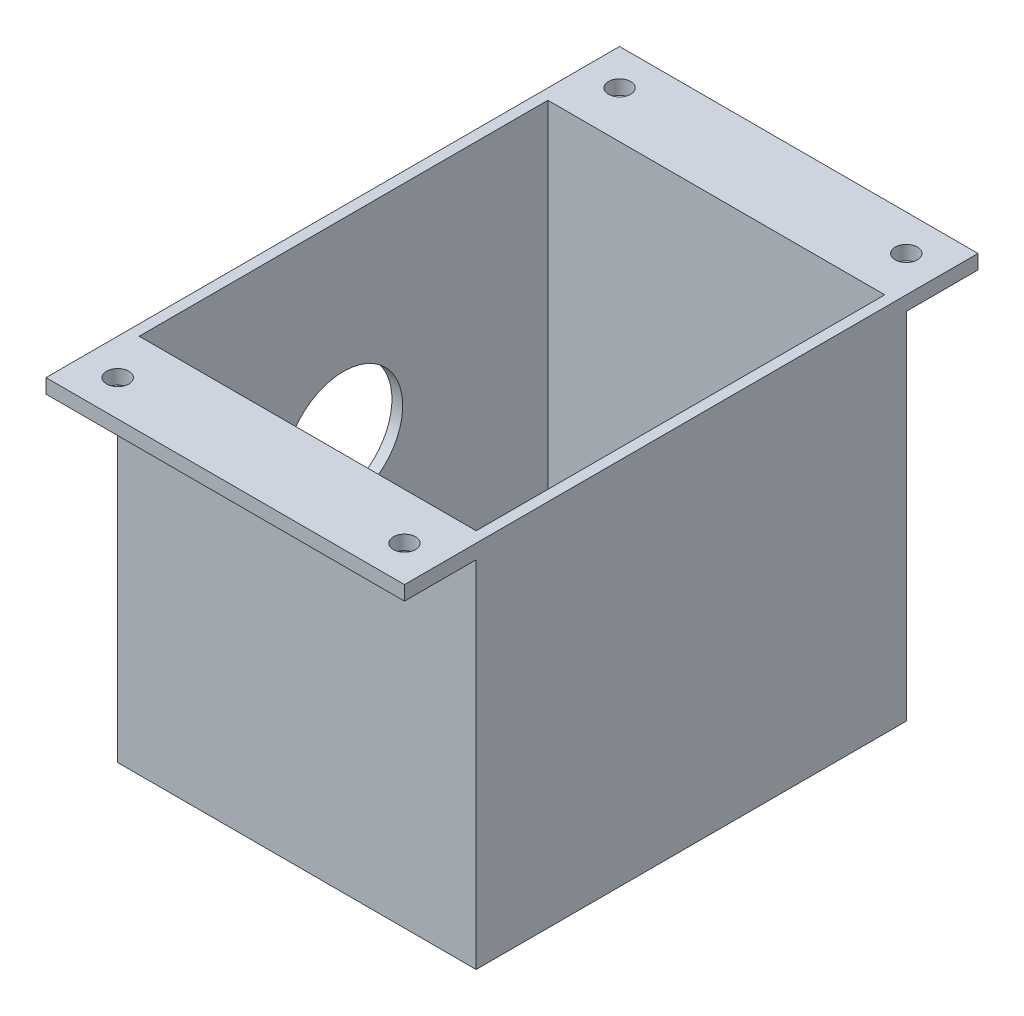
SolidWorks part; units mm, degrees
ref_plane "Płaszczyzna przednia" through (0, 0, 0) normal (0, 0, 1) x (1, 0, 0)
ref_plane "Płaszczyzna górna" through (0, 0, 0) normal (0, 1, 0) x (1, 0, 0)
ref_plane "Płaszczyzna prawa" through (0, 0, 0) normal (1, 0, 0) x (0, 0, -1)
sketch "Sketch1" plane through (0, 0, 0) normal (0, 1, 0) x (1, 0, 0)
  line L9 (-25, -40) -> (25, -40)
  line L16 (-25, -40) -> (-25, 40)
  line L21 (-25, 40) -> (25, 40)
  line L23 (25, -40) -> (25, 40)
  line L24 (-23.5, -28.5) -> (23.5, -28.5)
  line L25 (-23.5, -28.5) -> (-23.5, 28.5)
  line L26 (-25, -30) -> (25, -30)
  line L27 (-25, -30) -> (-25, 30)
  line L28 (-25, 30) -> (25, 30)
  line L29 (25, -30) -> (25, 30)
  line L30 (-23.5, 28.5) -> (23.5, 28.5)
  line L31 (23.5, -28.5) -> (23.5, 28.5)
  line L32 (-23.5, -28.5) -> (23.5, 28.5) construction
  line L33 (-23.5, 28.5) -> (23.5, -28.5) construction
  point P0 (0, 0)
  point P1 (0, 0)
  point P5 (0, 0)
  point P8 (0, 0)
  point P11 (0, 0)
  point P14 (0, 0)
  dimension "D1" = 50
  dimension "D2" = 80
  dimension "D3" = 50
  dimension "D4" = 60
  dimension "D5" = 47
  dimension "D6" = 57
extrude "Boss-Extrude6" add sketch "Sketch1" along normal blind 50 contours L28 L16 L26 L23 L31 L24 L25 L30 region at (-24.219, 0, 0)
sketch "Sketch7" plane through (0, 0, 0) normal (0, -1, 0) x (1, 0, 0)
  line L1 (-25, 30) -> (25, 30)
  line L2 (-25, 30) -> (-25, -30)
  line L3 (-25, -30) -> (25, -30)
  line L4 (25, 30) -> (25, -30)
extrude "Boss-Extrude8" add sketch "Sketch7" along normal blind 1.5
sketch "Sketch8" plane through (25, 0, 0) normal (1, 0, 0) x (0, 0, -1)
  line L1 (-30, 50) -> (-40, 50)
  line L2 (-30, 50) -> (-30, 48)
  line L3 (-30, 48) -> (-40, 48)
  line L4 (-40, 50) -> (-40, 48)
  line L5 (30, 50) -> (40, 50)
  line L6 (30, 50) -> (30, 48)
  line L7 (30, 48) -> (40, 48)
  line L8 (40, 50) -> (40, 48)
  dimension "D1" = 10
  dimension "D2" = 2
  dimension "D3" = 10
  dimension "D4" = 2
extrude "Boss-Extrude9" add sketch "Sketch8" against normal blind 50
sketch "Sketch9" plane through (0, 50, 0) normal (0, 1, 0) x (1, 0, 0)
  circle A0 centre (-20, 35) radius 1.55
  circle A1 centre (20, 35) radius 1.55
  circle A2 centre (20, -35) radius 1.55
  circle A3 centre (-20, -35) radius 1.55
  point P0 (0, 0)
  dimension "D1" = 40
  dimension "D2" = 70
extrude "Cut-Extrude1" cut sketch "Sketch9" against normal blind 3
sketch "Sketch11" plane through (-25, 0, 0) normal (-1, 0, 0) x (0, 0, 1)
  line L0 (-30, 23.25) -> (30, 23.25) construction
  line L1 (-30, 48) -> (-30, -1.5) construction
  line L2 (30, 48) -> (30, -1.5) construction
  line L4 (40, 50) -> (-40, 50) construction
  line L5 (0, 50) -> (0, -1.5) construction
  line L6 (30, -1.5) -> (-30, -1.5) construction
  circle A0 centre (0, 23.25) radius 8.25
  point P6 (0, 23.25)
extrude "Cut-Extrude3" cut sketch "Sketch11" against normal blind 1.5
